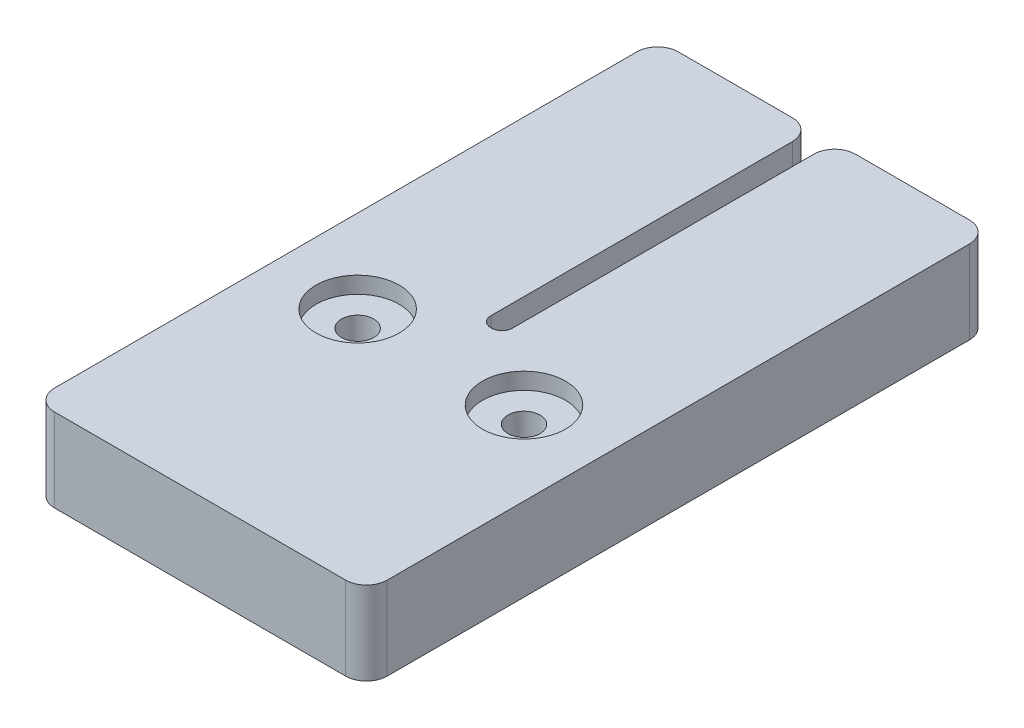
SolidWorks part; units mm, degrees
material "PE High Density"
ref_plane "Front Plane" through (0, 0, 0) normal (0, 0, 1) x (1, 0, 0)
ref_plane "Top Plane" through (0, 0, 0) normal (0, 1, 0) x (1, 0, 0)
ref_plane "Right Plane" through (0, 0, 0) normal (1, 0, 0) x (0, 0, -1)
sketch "Sketch1" plane through (0, 0, 0) normal (0, 1, 0) x (1, 0, 0)
  line L0 (-25.4, 0) -> (25.4, 0)
  line L1 (25.4, 0) -> (25.4, 95.25)
  line L2 (25.4, 95.25) -> (1.651, 95.25)
  line L5 (-1.651, 95.25) -> (-25.4, 95.25)
  line L6 (-25.4, 95.25) -> (-25.4, 0)
  line L7 (-1.651, 95.25) -> (-1.651, 44.45)
  line L8 (-1.651, 44.45) -> (1.651, 44.45)
  line L9 (1.651, 44.45) -> (1.651, 95.25)
  dimension "D1" = 50.8
  dimension "D2" = 95.25
  dimension "D3" = 3.302
  dimension "D4" = 50.8
extrude "Boss-Extrude1" add sketch "Sketch1" along normal blind 12.7
fillet "Fillet1" radius 3.175 6 edges at (1.651, 6.35, -95.25) (-1.651, 6.35, -95.25) (-25.4, 6.35, -95.25) (25.4, 6.35, -95.25) (-25.4, 6.35, 0) (25.4, 6.35, 0)
fillet "Fillet2" radius 1.5875 2 edges at (-1.651, 6.35, -44.45) (1.651, 6.35, -44.45)
sketch "Sketch2" plane through (0, 0, 0) normal (0, -1, 0) x (1, 0, 0)
  line L0 (-22.225, 0) -> (22.225, 0) construction
  circle A0 centre (-12.7, -36.7538) radius 2.4575
  circle A1 centre (12.7, -36.7538) radius 2.4575
  dimension "D1" = 4.9149
  dimension "D2" = 36.7538
  dimension "D3" = 12.7
  dimension "D4" = 12.7
extrude "Cut-Extrude1" cut sketch "Sketch2" against normal through all contours A0 | A1
sketch "Sketch3" plane through (0, 12.7, 0) normal (0, 1, 0) x (1, 0, 0)
  circle A0 centre (12.7, 36.7538) radius 6.35
  circle A1 centre (-12.7, 36.7538) radius 6.35
  circle A2 centre (-12.7, 36.7538) radius 2.4575 construction
  circle A3 centre (12.7, 36.7538) radius 2.4575 construction
  dimension "D1" = 12.7
extrude "Cut-Extrude2" cut sketch "Sketch3" against normal blind 2.54
